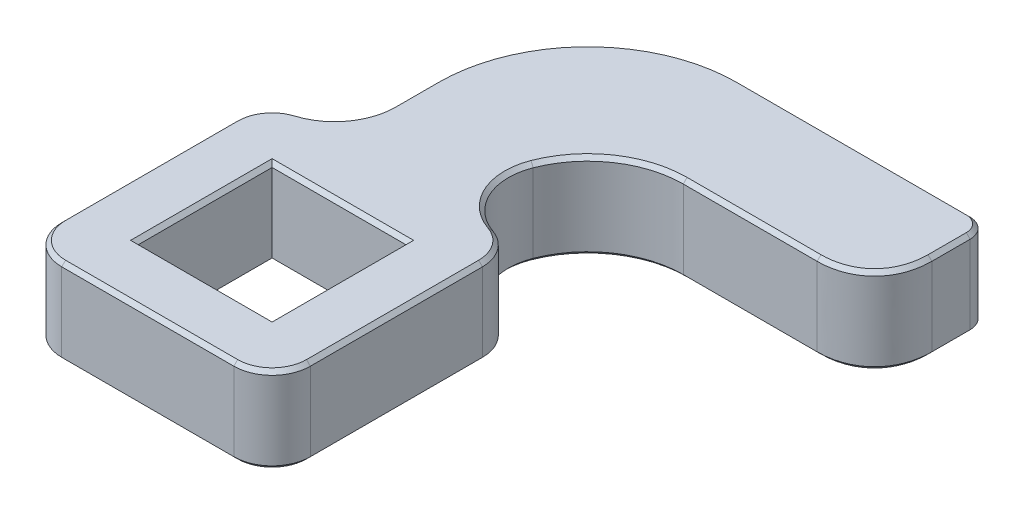
SolidWorks part; units mm, degrees
ref_plane "前视基准面" through (0, 0, 0) normal (0, 0, 1) x (1, 0, 0)
ref_plane "上视基准面" through (0, 0, 0) normal (0, 1, 0) x (1, 0, 0)
ref_plane "右视基准面" through (0, 0, 0) normal (1, 0, 0) x (0, 0, -1)
other "Configuration Table"
sketch "草图1" plane through (0, 0, 0) normal (0, 1, 0) x (1, 0, 0)
  line L0 (9.5, 13) -> (13, 13)
  line L1 (0, 0) -> (13, 0)
  line L2 (0, 0) -> (0, 13)
  line L3 (0, 13) -> (3.5, 13)
  line L4 (13, 0) -> (13, 13)
  line L6 (3.5, 13) -> (3.5, 26)
  line L7 (3.5, 26) -> (9.5, 26)
  line L8 (9.5, 13) -> (9.5, 26)
  line L10 (3, 10) -> (10, 10)
  line L11 (3, 10) -> (3, 3)
  line L12 (3, 3) -> (10, 3)
  line L13 (10, 10) -> (10, 3)
  point P7 (6.5, 0)
  point P12 (6.5, 26)
  point P15 (6.5, 10)
  point P16 (10, 6.5)
  point P17 (13, 6.5)
  dimension "D1" = 0
  dimension "D3" = 0
  dimension "D4" = 7
  dimension "D2" = 13
  dimension "D5" = 13
  dimension "D6" = 6
  dimension "D7" = 0
  dimension "D8" = 13
  dimension "D9" = 7
extrude "凸台-拉伸1" add sketch "草图1" along normal blind 4.5
sketch "草图4" plane through (9.5, 0, 0) normal (1, 0, 0) x (0, 0, -1)
  line L0 (13, 0) -> (26, 0) construction
  line L1 (26, 4.5) -> (20, 4.5)
  line L2 (26, 4.5) -> (26, 0)
  line L3 (26, 0) -> (20, 0)
  line L4 (20, 4.5) -> (20, 0)
  dimension "D1" = 6
extrude "凸台-拉伸4" add sketch "草图4" along normal blind 15
fillet "圆角1" radius 3 1 edges at (24.5, 2.25, -20) conic rho 0.45
fillet "圆角3" radius 5 1 edges at (9.5, 2.25, -20)
fillet "圆角4" radius 8 1 edges at (3.5, 2.25, -26)
fillet "圆角5" radius 2 4 edges at (13, 2.25, 0) (0, 2.25, 0) (13, 2.25, -13) (0, 2.25, -13)
fillet "圆角6" radius 3 2 edges at (9.5, 2.25, -13) (3.5, 2.25, -13)
fillet "圆角7" radius 1 1 edges at (24.5, 2.25, -26)
chamfer "倒角3" distance 0.2 angle 45 42 edges at (11.6769, 4.5, -19.1267) (12.6292, 4.5, -12.16) (13, 4.5, -6.5) (12.4142, 4.5, -0.5858) (6.5, 4.5, 0) (0.5858, 4.5, -0.5858) (0, 4.5, -6.5) (0.3875, 4.5, -12.1832) (3.5, 4.5, -16.8848) (5.8431, 4.5, -23.6569) (17.5, 4.5, -26) (24.2071, 4.5, -25.7071) (5.8431, 0, -23.6569) (3.5, 0, -16.8848) (0.3875, 0, -12.1832) (0, 0, -6.5) (0.5858, 0, -0.5858) (6.5, 0, 0) (12.4142, 0, -0.5858) (13, 0, -6.5) (12.6292, 0, -12.16) (11.6769, 0, -19.1267) (24.2071, 0, -25.7071) (17.5, 0, -26) (10, 0, -6.5) (6.5, 0, -3) (3, 0, -6.5) (6.5, 0, -10) (6.5, 4.5, -3) (10, 4.5, -6.5) (6.5, 4.5, -10) (3, 4.5, -6.5) (2.9187, 0, -13.9949) (9.9132, 0, -14.4651) (9.9132, 4.5, -14.4651) (2.9187, 4.5, -13.9949)
